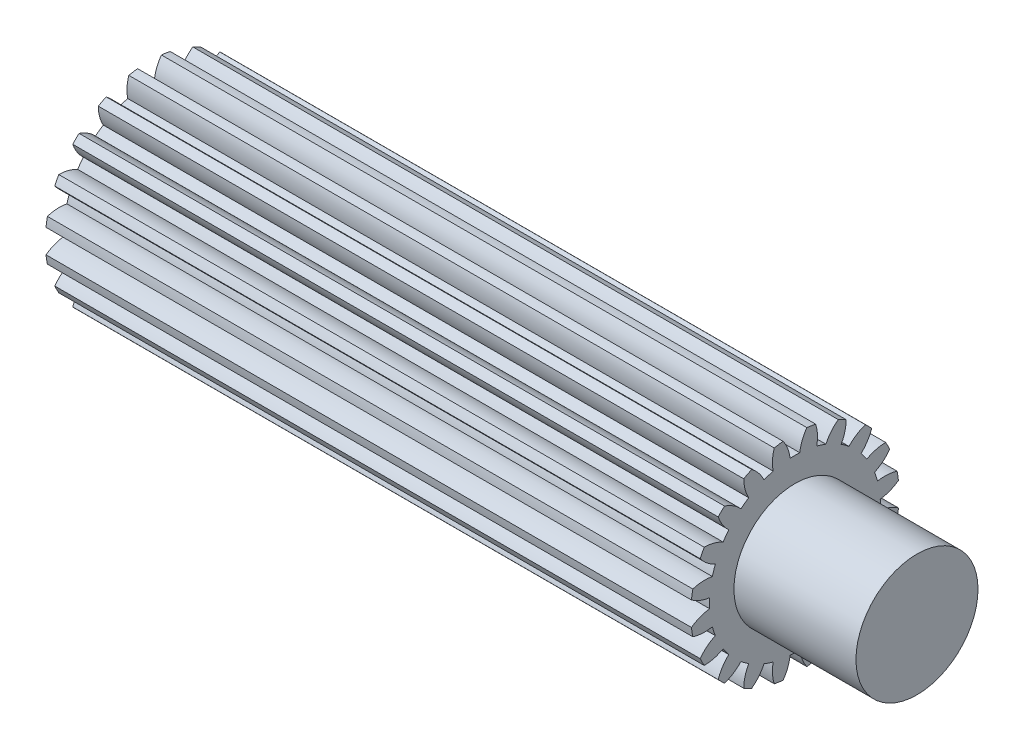
SolidWorks part; units mm, degrees
ref_plane "Plane1" through (0, 0, 0) normal (0, 0, 1) x (1, 0, 0)
ref_plane "Plane2" through (0, 0, 0) normal (0, 1, 0) x (1, 0, 0)
ref_plane "Plane3" through (0, 0, 0) normal (1, 0, 0) x (0, 0, -1)
sketch "HoldingSke" plane through (0, 0, 0) normal (0, 1, 0) x (1, 0, 0)
  line L0 (0, 0) -> (0.4698, -0.171)
  line L1 (-15, 0) -> (100, 0) construction
  line L2 (0, 0) -> (-2.1039, 2.3779)
  line L3 (0, 0) -> (-11.863, 4.5341)
  line L4 (0, 0) -> (8.1152, 2.9537)
  line L5 (0, 0) -> (-46.8476, -17.4728)
  line L6 (0, 0) -> (-9.9476, -6.7116)
  line L7 (-2.1039, 2.3779) -> (8.6586, 51.2059)
  line L8 (-76.2, 54.61) -> (-76.1, 54.61)
  line L9 (-71.009, 38.7566) -> (-53.1078, 45.2721)
  line L10 (-76.2, 71.12) -> (104.1128, 71.12)
  line L11 (0, 0) -> (-12, 0)
  line L12 (-76.2, 101.6) -> (-76.133, 101.6)
  line L13 (24.9733, 27.94) -> (52.9518, 28.4284)
  line L14 (24.9733, 27.94) -> (24.9743, 27.94)
  line L15 (24.9733, 27.94) -> (100.4006, 29.5858)
  line L16 (-63.627, -2) -> (-12.827, -2)
  circle A0 centre (0, 0) radius 0.4
  circle A1 centre (0, 0) radius 17.499
  circle A2 centre (0, 0) radius 37.5
  circle A3 centre (0, 0) radius 0.4
  dimension "Num_teeth" = 20
  dimension "Pitch_radius" = 180.3128
  dimension "Width" = 12
sketch "BasProSke" plane through (0, 0, 0) normal (0, 1, 0) x (1, 0, 0)
  line L0 (-10, 0) -> (60, 0) construction
  line L1 (0, 0) -> (0, 22)
  line L2 (0, 0) -> (132.2299, 0)
  line L3 (132.2299, 0) -> (132.2299, 22)
  line L4 (132.2299, 22) -> (0, 22)
  dimension "Thickness" = 132.2299
  dimension "Diameter" = 44
revolve "Base-Revolve" add sketch "BasProSke" angle 360 about L0
sketch "TooCutSke" plane through (0, 0, 0) normal (1, 0, 0) x (0, 0, -1)
  line L1 (0, 0) -> (0, 107) construction
  line L2 (0, 0) -> (-1.6864, 19.9288) construction
  line L3 (0, 0) -> (-6.2409, 39.4033) construction
  line L4 (-1.6864, 19.9288) -> (-3.1204, 19.7016) construction
  arc A0 (0.9862, 17.4712) -> (-0.9862, 17.4712) centre (0, 0) ccw
  arc A1 (2.9329, 21.8293) -> (-2.9329, 21.8293) centre (0, 0) ccw
  circle A2 centre (0, 0) radius 20 construction
  circle A3 centre (0, 0) radius 18.7939 construction
  arc A4 (-0.9862, 17.4712) -> (-2.9329, 21.8293) centre (-8.9313, 16.536) ccw
  arc A5 (2.9329, 21.8293) -> (0.9862, 17.4712) centre (8.9313, 16.536) ccw
extrude "ToothCut" cut sketch "TooCutSke" along normal through all
fillet "Breaks" [suppressed] radius 0.04 tangent propagation no
fillet "RootFillets" [suppressed] radius 0.501
pattern_circular "TeethCuts" count 20 every 18 about axis through (-10, 0, 0) along (1, 0, 0) of "ToothCut", "RootFillets", "Breaks"
sketch "HubNeaOneSke" plane through (0, 0, 0) normal (-1, 0, 0) x (0, 0, 1)
  circle A0 centre (0, 0) radius 17.499
  dimension "Diameter" = 34.998
extrude "HubNearOne" [suppressed] add sketch "HubNeaOneSke" along normal blind 38.0001
sketch "HubNeaBotSke" plane through (0, 0, 0) normal (-1, 0, 0) x (0, 0, 1)
  circle A0 centre (0, 0) radius 17.499
  dimension "Diameter" = 34.998
extrude "HubNearBoth" [suppressed] add sketch "HubNeaBotSke" along normal blind 19
ref_plane "FarPln" through (132.2299, 0, 0) normal (1, 0, 0) x (0, 0, -1)
sketch "HubFarSke" plane through (132.2299, 0, 0) normal (1, 0, 0) x (0, 0, -1)
  circle A0 centre (0, 0) radius 17.499
  dimension "Diameter" = 34.998
extrude "HubFar" [suppressed] add sketch "HubFarSke" along normal blind 19
sketch "BorSke" plane through (0, 0, 0) normal (1, 0, 0) x (0, 0, -1)
  circle A0 centre (0, 0) radius 0.4
  dimension "Diameter" = 0.8
extrude "Bore" cut sketch "BorSke" along normal mid plane 100.0001
sketch "KeySke" plane through (0, 0, 0) normal (1, 0, 0) x (0, 0, -1)
  line L0 (-0.05, 0) -> (-0.05, 0.5)
  line L1 (-0.05, 0.5) -> (0.05, 0.5)
  line L2 (0.05, 0.5) -> (0.05, 0)
  line L3 (0, 0) -> (0, 34) construction
  line L4 (-0.05, 0) -> (0.05, 0)
  dimension "Width" = 0.1
extrude "Keyway" [suppressed] cut sketch "KeySke" along normal mid plane 100.0001
pattern_circular "Keyway2" [suppressed] count 2 every 90 about axis through (-10, 0, 0) along (1, 0, 0) reverse direction yes
sketch "Sketch1" plane through (132.2299, 0, 0) normal (1, 0, 0) x (0, 0, -1)
  circle A0 centre (0, 0) radius 21.3427
  circle A1 centre (0, 0) radius 22
extrude "Cut-Extrude1" cut sketch "Sketch1" against normal through all
scale "Scale1" scale about origin uniform scaling yes scale factor 0.4
sketch "Sketch6" plane through (52.892, 0, 0) normal (1, 0, 0) x (0, 0, -1)
  circle A0 centre (0, 0) radius 5
extrude "Boss-Extrude3" add sketch "Sketch6" along normal blind 10
sketch "Sketch7" plane through (0, 0, 0) normal (-1, 0, 0) x (0, 0, 1)
  line L1 (2.5, 0) -> (2.5, 4.3301)
  line L2 (2.5, 0) -> (2.5, -4.3301)
  arc A1 (2.5, 4.3301) -> (2.5, -4.3301) centre (0, 0) ccw
extrude "Cut-Extrude2" cut sketch "Sketch7" against normal blind 10
equation "' \"Module@HoldingSke\" = 6.35"
equation "' \"Num_teeth@HoldingSke\" = 12"
equation "' \"Ap@HoldingSke\" =  20"
equation "' \"Ap@HoldingSke\" = 20"
equation "' \"Width@HoldingSke\" = 0.5 * 25.4"
equation "' \"Hub_dia@HoldingSke\"= 1 * 25.4"
equation "' \"Hub_dia@HoldingSke\" = 1 * 25.4"
equation "' \"Overall_len@HoldingSke\" = 1.0 * 25.4"
equation "' \"Bore@HoldingSke\" = 0.75 * 25.4"
equation "' \"T_dim@HoldingSke\" = 0.1 * 25.4"
equation "' \"Width@KeySke\" = 0.25 * 25.4"
equation "' \"Show_teeth@HoldingSke\" = 13"
equation "' \"Backlash@HoldingSke\" = 0.009 * 25.4"
equation "' \"Addendum_fac@HoldingSke\" = 1.0"
equation "' \"Dedendum_fac@HoldingSke\" = 1.25"
equation "' \"Dedendum_add@HoldingSke\" = 0.00005 * 25.4"
equation "' \"Clearance_fac@HoldingSke\" = 0.25"
equation "\"Pitch@HoldingSke\" = 1 / \"Module@HoldingSke\""
equation "\"Overcut_dia@TooCutSke\" = (\"Num_teeth@HoldingSke\" + 2 * \"Addendum_fac@HoldingSke\") / \"Pitch@HoldingSke\" + 0.002 * 25.4"
equation "\"Pitch_dia@TooCutSke\" = \"Num_teeth@HoldingSke\" / \"Pitch@HoldingSke\""
equation "\"Base_dia@TooCutSke\" = \"Num_teeth@HoldingSke\" / \"Pitch@HoldingSke\" * cos((\"Ap@HoldingSke\"  * 3.14159265 / 180))"
equation "\"Root_dia@TooCutSke\" = (\"Num_teeth@HoldingSke\" + 2) / \"Pitch@HoldingSke\" - 2 * (\"Addendum_fac@HoldingSke\" + \"Dedendum_fac@HoldingSke\") / \"Pitch@HoldingSke\" - \"Dedendum_add@HoldingSke\" * 2"
equation "\"Half_ang@TooCutSke\" = 180 / \"Num_teeth@HoldingSke\""
equation "\"Half_CT@TooCutSke\" = \"Num_teeth@HoldingSke\" / \"Pitch@HoldingSke\" * sin((3.14159265 / 2 / \"Num_teeth@HoldingSke\")) / 2 - 7 * \"Backlash@HoldingSke\" / 4"
equation "\"Flank_rad@TooCutSke\" = \"Num_teeth@HoldingSke\" / \"Pitch@HoldingSke\" / 5"
equation "\"Radius@RootFillets\" = \"Clearance_fac@HoldingSke\" / \"Pitch@HoldingSke\" + \"Dedendum_add@HoldingSke\""
equation "\"Break_rad@Breaks\" = 0.02 / \"Pitch@HoldingSke\""
equation "\"Thickness@HoldingSke\" = \"Width@HoldingSke\""
equation "\"OAL@HoldingSke\" = \"Thickness@HoldingSke\""
equation "\"MHD@HoldingSke\" = (\"Num_teeth@HoldingSke\" + 2) / \"Pitch@HoldingSke\" - 2 * (\"Addendum_fac@HoldingSke\" + \"Dedendum_fac@HoldingSke\")  / \"Pitch@HoldingSke\" - \"Dedendum_add@HoldingSke\" * 2"
equation "\"MBD@HoldingSke\" = (\"Num_teeth@HoldingSke\" + 2) / \"Pitch@HoldingSke\" - 2 * (\"Addendum_fac@HoldingSke\" + \"Dedendum_fac@HoldingSke\")  / \"Pitch@HoldingSke\" - \"Dedendum_add@HoldingSke\" * 2 - 0.002 * 25.4"
equation "\"MHD@HoldingSke\" = ((sgn( \"MHD@HoldingSke\" - \"Hub_dia@HoldingSke\" )-1)*( \"MHD@HoldingSke\" - \"Hub_dia@HoldingSke\" ))/-2+ \"Hub_dia@HoldingSke\""
equation "\"MBD@HoldingSke\" = ((sgn( \"MBD@HoldingSke\" - \"Bore@HoldingSke\" )-1)*( \"MBD@HoldingSke\" - \"Bore@HoldingSke\" ))/-2+ \"Bore@HoldingSke\""
equation "\"OAL@HoldingSke\" = ((sgn( \"OAL@HoldingSke\" - \"Overall_len@HoldingSke\" )+1)*( \"OAL@HoldingSke\" - \"Overall_len@HoldingSke\" ))/2 + \"Overall_len@HoldingSke\" + 0.000002 * 25.4"
equation "\"Num_teeth@TeethCuts\" = int( \"Show_teeth@HoldingSke\" ) + 1"
equation "\"Num_teeth@TeethCuts\" = ((sgn( \"Num_teeth@TeethCuts\" - \"Num_teeth@HoldingSke\" )-1)*( \"Num_teeth@TeethCuts\" - \"Num_teeth@HoldingSke\" ))/-2+ \"Num_teeth@HoldingSke\""
equation "\"Num_teeth@TeethCuts\" = ((sgn( \"Num_teeth@TeethCuts\" - 2.0)+1)*( \"Num_teeth@TeethCuts\" - 2.0))/2 +2.0"
equation "\"Angle@TeethCuts\" = 360.0 / \"Num_teeth@HoldingSke\""
equation "\"Diameter@BasProSke\" = (\"Num_teeth@HoldingSke\" + 2 * \"Addendum_fac@HoldingSke\") / \"Pitch@HoldingSke\""
equation "' \"Fillet_rad@BasProSke\" =  \"Thickness@HoldingSke\" * 0.05"
equation "' \"Fillet_rad@BasProSke\" = \"Thickness@HoldingSke\" * 0.05"
equation "\"MHD@HoldingSke\" = ((sgn( \"MHD@HoldingSke\" - \"Root_dia@TooCutSke\" )-1)*( \"MHD@HoldingSke\" - \"Root_dia@TooCutSke\" ))/-2+ \"Root_dia@TooCutSke\""
equation "\"Diameter@HubNeaOneSke\" = \"MHD@HoldingSke\""
equation "\"Length@HubNearOne\" = \"OAL@HoldingSke\" - \"Thickness@BasProSke\""
equation "\"Diameter@HubNeaBotSke\" = \"MHD@HoldingSke\""
equation "\"Length@HubNearBoth\" = ( \"OAL@HoldingSke\" - \"Thickness@BasProSke\" ) / 2.0"
equation "\"Thickness@FarPln\" = \"Thickness@BasProSke\""
equation "\"Diameter@HubFarSke\" = \"MHD@HoldingSke\""
equation "\"Length@HubFar\" = ( \"OAL@HoldingSke\" - \"Thickness@BasProSke\" ) / 2.0"
equation "\"Diameter@BorSke\" = \"MBD@HoldingSke\""
equation "\"D1@Bore\" = \"OAL@HoldingSke\" * 2.0"
equation "\"D1@Keyway\" = \"OAL@HoldingSke\" * 2.0"
equation "\"Offset@KeySke\" = \"T_dim@HoldingSke\" + \"MBD@HoldingSke\" / 2.0"
